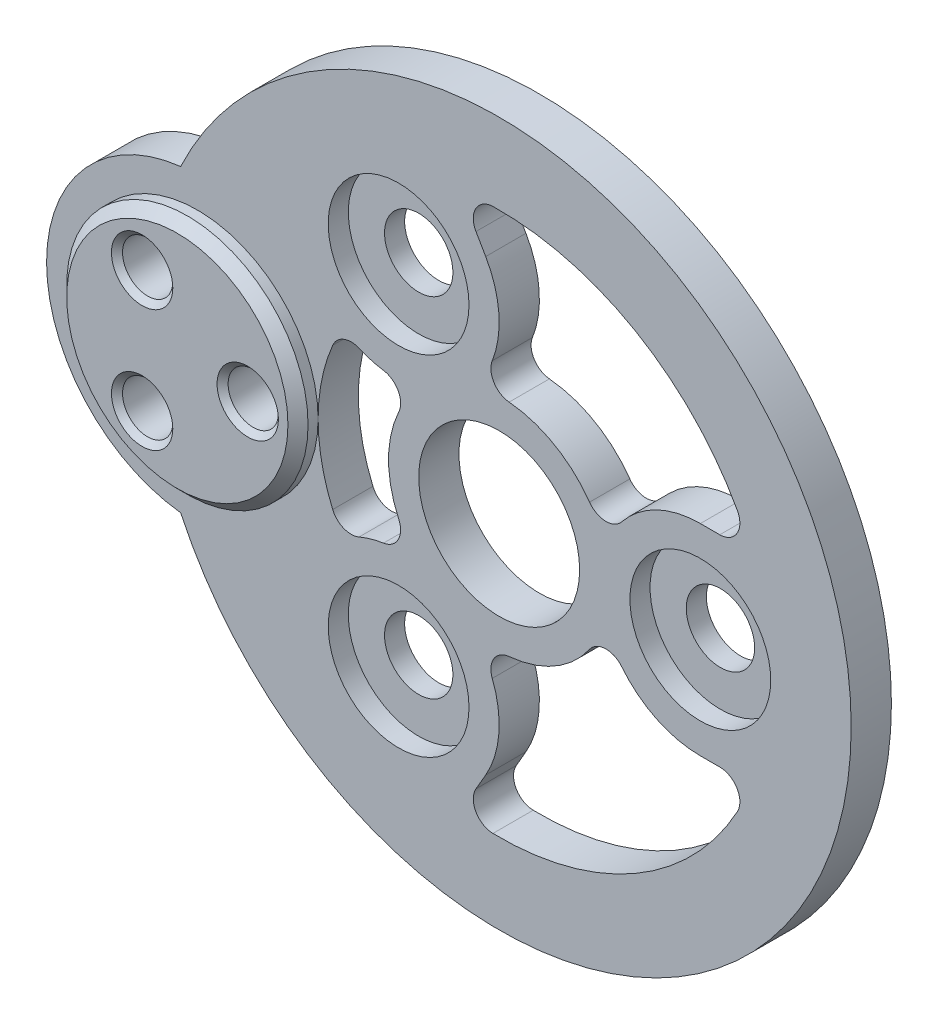
SolidWorks part; units mm, degrees
material "A2017"
ref_plane "正面" through (0, 0, 0) normal (0, 0, 1) x (1, 0, 0)
ref_plane "平面" through (0, 0, 0) normal (0, 1, 0) x (1, 0, 0)
ref_plane "右側面" through (0, 0, 0) normal (1, 0, 0) x (0, 0, -1)
sketch "ｽｹｯﾁ1" plane through (0, 0, 0) normal (0, 0, 1) x (1, 0, 0)
  line L0 (-15, 0) -> (0, 0) construction
  circle A0 centre (0, 0) radius 4
  arc A1 (-4.5, -6) -> (-4.5, 6) centre (0, 0) ccw
  arc A2 (-10.5, 6) -> (-10.5, -6) centre (-15, 0) ccw
  arc A3 (-10.5, 6) -> (-4.5, 6) centre (-7.5, 10) ccw
  arc A4 (-10.5, -6) -> (-4.5, -6) centre (-7.5, -10) cw
  dimension "D1" = 8
  dimension "D2" = 15
  dimension "D3" = 15
  dimension "D4" = 5
extrude "ﾎﾞｽ - 押し出し1" add sketch "ｽｹｯﾁ1" along normal blind 2
sketch "ｽｹｯﾁ6" plane through (0, 0, 2) normal (0, 0, 1) x (1, 0, 0)
  circle A0 centre (-15, 0) radius 6
  dimension "D1" = 12
extrude "ﾎﾞｽ - 押し出し3" add sketch "ｽｹｯﾁ6" along normal blind 1
sketch "ｽｹｯﾁ2" plane through (0, 0, 3) normal (0, 0, 1) x (1, 0, 0)
  circle A0 centre (-15, 0) radius 5 construction
  circle A1 centre (-11.5, 0) radius 1.5 construction
  circle A2 centre (-11.5, 0) radius 0.5
  dimension "D1" = 10
  dimension "D2" = 3
  dimension "D3" = 1
extrude "ｶｯﾄ - 押し出し1" cut sketch "ｽｹｯﾁ2" against normal blind 2
hole_wizard "M3x0.5 ねじ穴1" positions "ｽｹｯﾁ3" profile "ｽｹｯﾁ4" tap size "M3x0.5" standard "JIS" end condition through all
sketch "ｽｹｯﾁ3" plane through (0, 0, 3) normal (0, 0, 1) x (1, 0, 0)
  point P0 (-11.5, 0)
sketch "ｽｹｯﾁ4" plane through (-11.5, 0, 3) normal (1, 0, 0) x (0, -1, 0)
  line L0 (0, 0) -> (0, 3)
  line L1 (0, 3) -> (1.525, 3)
  line L2 (1.25, 2.725) -> (1.25, 0.275)
  line L3 (1.25, 0.275) -> (1.525, 0)
  line L5 (1.525, 0) -> (0, 0)
  line L6 (-1.25, 0.275) -> (-1.525, 0) construction
  line L7 (1.525, 3) -> (1.25, 2.725)
  line L8 (-1.525, 3) -> (-1.25, 2.725) construction
  line L11 (0, -6.35) -> (0, 107.95) construction
  dimension "次ｻｰﾌｪｽまでのねじ下穴ﾄﾞﾘﾙ直径" = 2.5
  dimension "次ｻｰﾌｪｽまでのねじ下穴ﾄﾞﾘﾙの深さ" = 3
  dimension "表面の皿穴の直径" = 3.05
  dimension "表面の皿穴の角度" = 90
  dimension "裏面の皿穴の直径" = 3.05
  dimension "裏面の皿穴の角度" = 90
cosmetic thread "穴のねじ山1" parameters "D2"=3
pattern_circular "円形ﾊﾟﾀｰﾝ1" count 3 over 360 about axis through (-15, 0, 2) along (0, 0, -1) of "M3x0.5 ねじ穴1"
chamfer "面取り1" distance 0.5 angle 45 1 edges at (-9, 0, 3)
chamfer "面取り2" [suppressed] distance 0.5 angle 45
chamfer "面取り3" [suppressed] distance 0.1 angle 45
sketch "ｽｹｯﾁ7" plane through (0, 0, 2) normal (0, 0, 1) x (1, 0, 0)
  circle A0 centre (0, 0) radius 17.5
  arc A5 (-10.5, 6) -> (-4.5, 6) centre (-7.5, 10) ccw
  arc A6 (-10.5, 6) -> (-10.5, -6) centre (-15, 0) ccw
  arc A7 (-4.5, -6) -> (-10.5, -6) centre (-7.5, -10) ccw
  arc A8 (-4.5, -6) -> (-4.5, 6) centre (0, 0) ccw
  arc A9 (-10.5, 6) -> (-4.5, 6) centre (-7.5, 10) ccw
  arc A10 (-10.5, 6) -> (-10.5, -6) centre (-15, 0) ccw
  arc A11 (-4.5, -6) -> (-10.5, -6) centre (-7.5, -10) ccw
  arc A12 (-4.5, -6) -> (-4.5, 6) centre (0, 0) ccw
  circle M5 centre (-15, 0) radius 6
  arc M6 (-4.5, 6) -> (-10.5, 6) centre (-7.5, 10) cw
  arc M7 (-10.5, 6) -> (-10.5, -6) centre (-15, 0) ccw
  arc M8 (-10.5, -6) -> (-4.5, -6) centre (-7.5, -10) cw
  arc M9 (-4.5, -6) -> (-4.5, 6) centre (0, 0) ccw
  circle M10 centre (0, 0) radius 4
  dimension "D1" = 35
  dimension "D2" = 0
extrude "ﾎﾞｽ - 押し出し4" add sketch "ｽｹｯﾁ7" against normal up to surface (2 mm away) contours A0 M7 M6 M9 M8 | A0 M7 M5 M8 M9 M6 M10 region at (3.7133, -16.6066, 2) region at (-13.1023, 6.9629, 2) up to face at (-17.5125, 4.3518, 0)
hole_wizard "M3 すきま穴1" positions "ｽｹｯﾁ9" profile "ｽｹｯﾁ10" hole size "M3" standard "JIS" end condition through all
sketch "ｽｹｯﾁ9" plane through (0, 0, 2) normal (0, 0, 1) x (1, 0, 0)
  point P0 (-5, 8.6603)
  point P3 (-5, -8.6603)
  point P6 (10, 0)
sketch "ｽｹｯﾁ10" plane through (-5, 8.6603, 2) normal (1, 0, 0) x (0, -1, 0)
  line L0 (0, 0) -> (0, 2)
  line L1 (0, 2) -> (1.7, 2)
  line L2 (1.7, 2) -> (1.7, 0)
  line L5 (1.7, 0) -> (0, 0)
  line L11 (0, -6.35) -> (0, 107.95) construction
  dimension "通し穴の直径" = 3.4
  dimension "通し穴の深さ" = 2
sketch "ｽｹｯﾁ11" plane through (0, 0, 2) normal (0, 0, 1) x (1, 0, 0)
  circle A0 centre (-5, 8.6603) radius 3.5
  circle A1 centre (10, 0) radius 3.5
  circle A2 centre (-5, -8.6603) radius 3.5
  point P11 (0, 0)
  dimension "D1" = 7
  dimension "D2" = 3
extrude "ｶｯﾄ - 押し出し3" cut sketch "ｽｹｯﾁ11" against normal blind 1
sketch "ｽｹｯﾁ12" plane through (0, 0, 2) normal (0, 0, 1) x (1, 0, 0)
  line L0 (10, 0) -> (13.5, 0) construction
  line L1 (10, 5) -> (13.5, 5)
  line L2 (10, -5) -> (13.5, -5)
  line L3 (-5, -8.6603) -> (-6.75, -11.6913) construction
  line L4 (-0.6699, -11.1603) -> (-2.4199, -14.1913)
  line L5 (-9.3301, -6.1603) -> (-11.0801, -9.1913)
  line L6 (-5, 8.6603) -> (-6.75, 11.6913) construction
  line L7 (-9.3301, 6.1603) -> (-11.0801, 9.1913)
  line L8 (-0.6699, 11.1603) -> (-2.4199, 14.1913)
  circle A0 centre (0, 0) radius 13.5
  circle A1 centre (0, 0) radius 5.5
  arc A2 (10, 5) -> (10, -5) centre (10, 0) ccw
  arc A3 (13.5, -5) -> (13.5, 5) centre (13.5, 0) ccw
  arc A4 (-0.6699, -11.1603) -> (-9.3301, -6.1603) centre (-5, -8.6603) ccw
  arc A5 (-11.0801, -9.1913) -> (-2.4199, -14.1913) centre (-6.75, -11.6913) ccw
  arc A6 (-9.3301, 6.1603) -> (-0.6699, 11.1603) centre (-5, 8.6603) ccw
  arc A7 (-2.4199, 14.1913) -> (-11.0801, 9.1913) centre (-6.75, 11.6913) ccw
  arc A8 (-0.3439, 6.8379) -> (0.4969, 5.4775) centre (0.5873, 6.4734) ccw
  arc A9 (4.4952, 3.1691) -> (6.0938, 3.1211) centre (5.3125, 3.7453) ccw
  arc A10 (0.4969, -5.4775) -> (-0.3439, -6.8379) centre (0.5873, -6.4734) ccw
  arc A11 (6.0938, -3.1211) -> (4.4952, -3.1691) centre (5.3125, -3.7453) ccw
  arc A12 (-4.9921, 2.3084) -> (-5.7498, 3.7168) centre (-5.8998, 2.7281) ccw
  arc A13 (-5.7498, -3.7168) -> (-4.9921, -2.3084) centre (-5.8998, -2.7281) ccw
  arc A14 (-7.7884, 4.51) -> (-7.7884, -4.51) centre (0, 0) ccw
  circle A15 centre (-15, 0) radius 6 construction
  point P7 (11.75, 0)
  point P16 (-5.875, -10.1758)
  point P23 (-5.875, 10.1758)
  point P28 (0, 0)
  point P48 (0, 0)
  dimension "D1" = 27
  dimension "D2" = 11
  dimension "D5" = 1
  dimension "D3" = 10
  dimension "D4" = 3
  dimension "D6" = 3
extrude "ｶｯﾄ - 押し出し4" cut sketch "ｽｹｯﾁ12" against normal through all contours A1 A9 A2 L1 A0 L8 A6 A8 | A2 A11 A1 A10 A4 L4 A0 L2 | A6 A14 A4 A13 A1 A12 region at (4.8059, 8.3241, 2) region at (4.8059, -8.3241, 2) region at (-7.0052, 0, 2)
fillet "ﾌｨﾚｯﾄ1" radius 1 6 edges at (12.5399, -5, 1) (-1.9398, -13.3599, 1) (12.5399, 5, 1) (-7.7884, -4.51, 1) (-7.7884, 4.51, 1) (-1.9398, 13.3599, 1)
